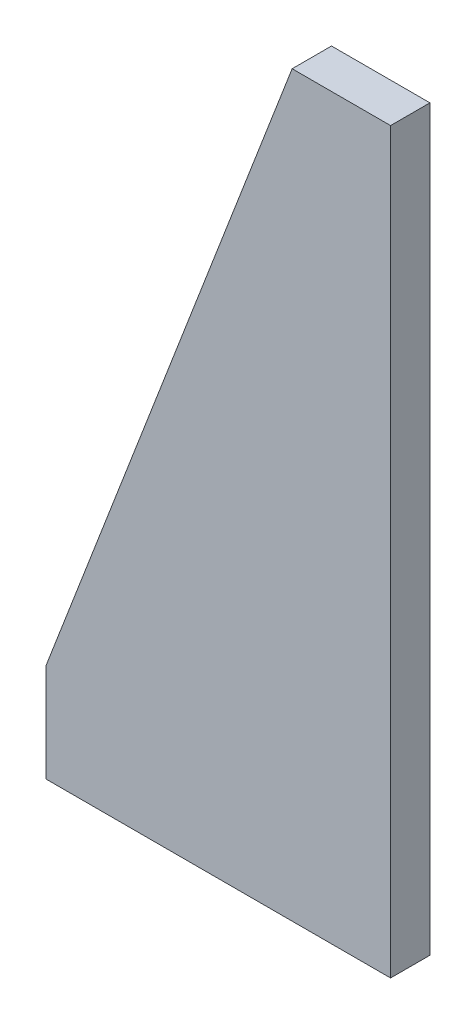
SolidWorks part; units mm, degrees
note: The reader was unsure of these and kept them because the rebuilt part matched: thickness of "Базовая кромка1", "Листовой металл1".
material "Простая углеродистая сталь"
ref_plane "Спереди" through (0, 0, 0) normal (0, 0, 1) x (1, 0, 0)
ref_plane "Сверху" through (0, 0, 0) normal (0, 1, 0) x (1, 0, 0)
ref_plane "Справа" through (0, 0, 0) normal (1, 0, 0) x (0, 0, -1)
sketch "Эскиз1" plane through (0, 0, 0) normal (0, 0, 1) x (1, 0, 0)
  line L0 (0, 0) -> (140, 0) construction
  line L1 (140, 0) -> (140, 20) construction
  line L2 (140, 20) -> (90, 150) construction
  line L3 (90, 150) -> (50, 150) construction
  line L4 (50, 150) -> (0, 20)
  line L5 (0, 20) -> (0, 0)
  line L6 (70, 0) -> (70, 178.6744) construction
  line L7 (0, 0) -> (70, 0)
  line L8 (70, 0) -> (70, 150)
  line L9 (70, 150) -> (50, 150)
  dimension "D1" = 70
  dimension "D2" = 150
  dimension "D3" = 20
  dimension "D4" = 20
base flange "Базовая кромка1" sketch "Эскиз1" thickness 8 reverse thickness direction no parameters "D1"=3
sketch "Сгиб-Линии1" [suppressed] plane through (0, 0, 0) normal (0, 1, 0) x (1, 0, 0)
sketch "Граничная рамка1" [suppressed] plane through (0, 0, 0) normal (0, 1, 0) x (1, 0, 0)
sheet metal parameters "Листовой металл1" thickness 8 parameters "D1"=3, "D7"=10
flat pattern "Развертка1" [suppressed]
sketch "Сгиб-Линии2" plane through (0, 0, 0) normal (0, 1, 0) x (1, 0, 0)
sketch3d "Граничная рамка2" [suppressed]
  line L0 (70, 150, 0) -> (70, 0, 0) construction
  line L1 (0, 150, 0) -> (0, 0, 0) construction
  line L2 (70, 150, 0) -> (0, 150, 0) construction
  line L3 (70, 0, 0) -> (0, 0, 0) construction
